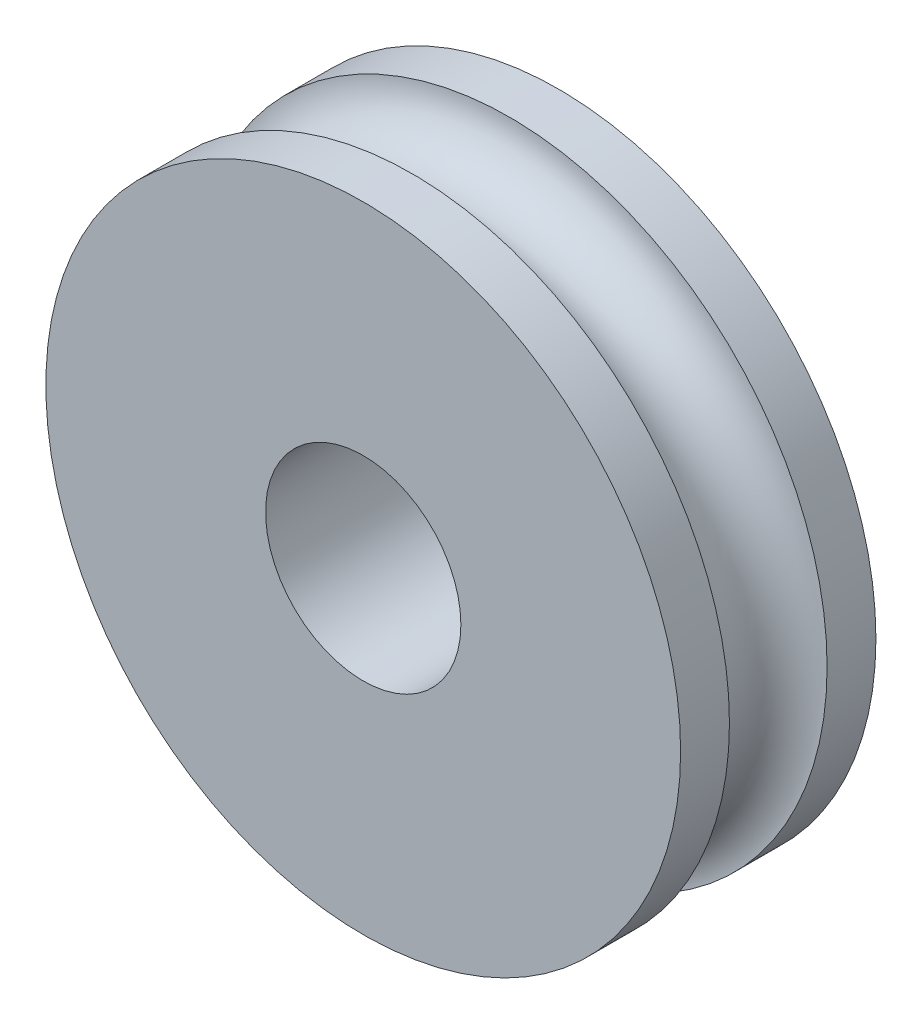
SolidWorks part; units mm, degrees
ref_plane "Front Plane" through (0, 0, 0) normal (0, 0, 1) x (1, 0, 0)
ref_plane "Top Plane" through (0, 0, 0) normal (0, 1, 0) x (1, 0, 0)
ref_plane "Right Plane" through (0, 0, 0) normal (1, 0, 0) x (0, 0, -1)
sketch "Sketch8" plane through (0, 0, 0) normal (0, 0, 1) x (1, 0, 0)
  circle A0 centre (0, 0) radius 6.5
  dimension "D1" = 13
extrude "Boss-Extrude2" add sketch "Sketch8" along normal blind 2 and the other way blind 2
sketch "Sketch9" plane through (0, 0, 0) normal (0, 0, 1) x (1, 0, 0)
  circle A0 centre (0, 0) radius 6.5
  dimension "D1" = 13
sweep "Cut-Sweep1" cut path "Sketch9" circular profile diameter 2 parameters "D3"=2
sketch "Sketch26" plane through (0, 0, 2) normal (0, 0, 1) x (1, 0, 0)
  circle A0 centre (0, 0) radius 2
  dimension "D1" = 4
extrude "Cut-Extrude1" cut sketch "Sketch26" against normal through all
